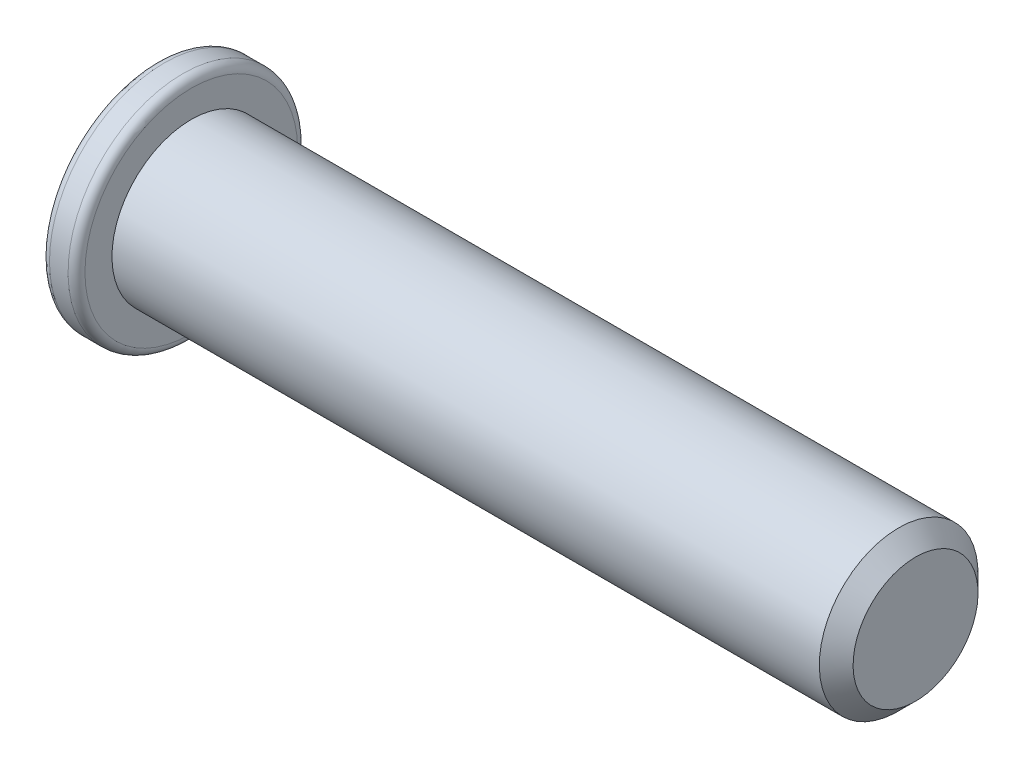
SolidWorks part; units mm, degrees
material "6061 Alloy"
ref_plane "Front Plane" through (0, 0, 0) normal (0, 0, 1) x (1, 0, 0)
ref_plane "Top Plane" through (0, 0, 0) normal (0, 1, 0) x (1, 0, 0)
ref_plane "Right Plane" through (0, 0, 0) normal (1, 0, 0) x (0, 0, -1)
sketch "Sketch1" plane through (0, 0, 0) normal (0, 0, 1) x (1, 0, 0)
  line L0 (0, 0) -> (0, 6.8)
  line L1 (0, 6.8) -> (2.1, 6.8)
  line L2 (2.1, 6.8) -> (2.1, 4.7)
  line L3 (2.1, 4.7) -> (45, 4.7)
  line L4 (45, 4.7) -> (45, 0)
  line L5 (45, 0) -> (0, 0)
  dimension "D1" = 6.8
  dimension "D2" = 2.1
  dimension "D3" = 45
  dimension "D4" = 4.7
revolve "Revolve1" add sketch "Sketch1" angle 360 about L5
cosmetic thread "Cosmetic Thread1" parameters "D1"=19.5, "D2"=6.891
chamfer "Chamfer1" distance 1 angle 45 1 edges at (45, 4.7, 0)
fillet "Fillet1" radius 0.5 2 edges at (2.1, 6.8, 0) (0, 6.8, 0)
